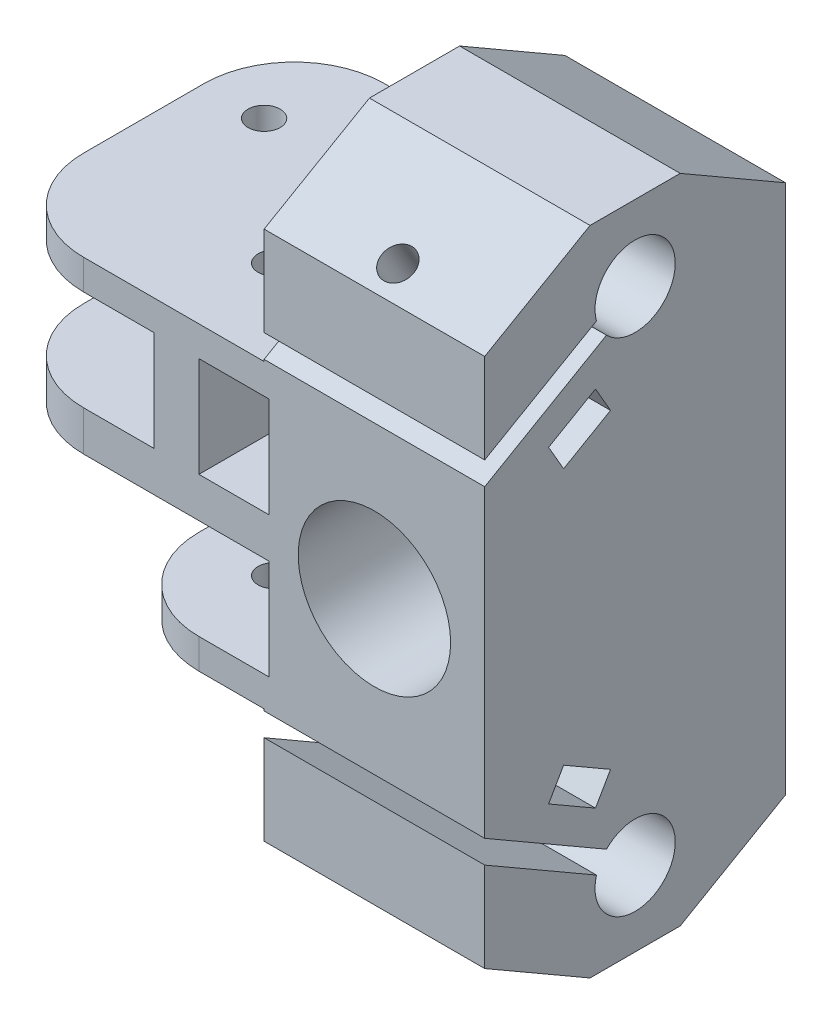
SolidWorks part; units mm, degrees
ref_plane "Plano frontal" through (0, 0, 0) normal (0, 0, 1) x (1, 0, 0)
ref_plane "Plano superior" through (0, 0, 0) normal (0, 1, 0) x (1, 0, 0)
ref_plane "Plano direito" through (0, 0, 0) normal (1, 0, 0) x (0, 0, -1)
sketch "Esboço2" plane through (0, 0, 0) normal (0, 0, 1) x (1, 0, 0)
  line L0 (-11, 15) -> (-11, 32.5)
  line L1 (-11, -32.5) -> (11, -32.5)
  line L2 (-11, -32.5) -> (-11, -15)
  line L3 (-11, 32.5) -> (11, 32.5)
  line L4 (11, -32.5) -> (11, 32.5)
  line L5 (-11, -32.5) -> (11, 32.5) construction
  line L6 (-11, 32.5) -> (11, -32.5) construction
  line L7 (-38, 15) -> (-11, 15)
  line L8 (-38, 15) -> (-38, 12)
  line L9 (-26.5, -15) -> (-11, -15)
  line L10 (0, 0) -> (-50.7474, 0) construction
  line L11 (-38, 15) -> (-11, -15) construction
  line L12 (-38, -15) -> (-11, 15) construction
  line L13 (-17.5, 2) -> (-10.5, 2)
  line L14 (-17.5, 2) -> (-17.5, 12)
  line L15 (-17.5, 12) -> (-10.5, 12)
  line L16 (-10.5, 2) -> (-10.5, 12)
  line L17 (-17.5, 2) -> (-10.5, 12) construction
  line L18 (-17.5, 12) -> (-10.5, 2) construction
  line L19 (-22, 12) -> (-38, 12)
  line L20 (-22, 12) -> (-22, 2)
  line L21 (-22, 2) -> (-38, 2)
  line L22 (-38, -2) -> (-26.5, -2)
  line L23 (-22, 12) -> (-38, 2) construction
  line L24 (-22, 2) -> (-38, 12) construction
  line L25 (-10.5, -2) -> (-26.5, -2)
  line L26 (-10.5, -2) -> (-10.5, -12)
  line L27 (-10.5, -12) -> (-26.5, -12)
  line L29 (-26.5, -12) -> (-26.5, -15)
  line L31 (-38, 2) -> (-38, -2)
  line L33 (-10.5, -2) -> (-26.5, -12) construction
  line L34 (-10.5, -12) -> (-26.5, -2) construction
  circle A0 centre (0, 0) radius 7.6
  point P7 (-24.5, 0)
  point P12 (-14, 7)
  point P18 (-30, 7)
  point P23 (-26.5, -15)
  point P26 (-18.5, -7)
  dimension "D1" = 15.2
  dimension "D2" = 65
  dimension "D3" = 22
  dimension "D4" = 30
  dimension "D5" = 27
  dimension "D6" = 3
  dimension "D7" = 7
  dimension "D9" = 16
  dimension "D10" = 0.5
  dimension "D11" = 10
  dimension "D12" = 3
extrude "Ressalto-extrusão1" add sketch "Esboço2" along normal blind 30
sketch "Esboço3" plane through (-11, 0, 0) normal (-1, 0, 0) x (0, 0, 1)
  line L0 (0, 0) -> (30, 0) construction
  line L1 (30, 15) -> (0, 15) construction
  line L2 (30, 26.4348) -> (19.4948, 32.5)
  line L3 (30, 32.5) -> (30, 15) construction
  line L4 (15, 32.5) -> (15, 15) construction
  line L5 (18.9522, 18.0994) -> (23.6287, 15.3994)
  line L6 (18.9522, 18.0994) -> (17.4522, 15.5013)
  line L7 (17.4522, 15.5013) -> (22.1287, 12.8013)
  line L8 (23.6287, 15.3994) -> (22.1287, 12.8013)
  line L9 (18.9522, 18.0994) -> (22.1287, 12.8013) construction
  line L10 (17.4522, 15.5013) -> (23.6287, 15.3994) construction
  line L12 (18.3535, 23.0639) -> (31.633, 15.3969) construction
  line L13 (17.8541, 22.1975) -> (31.133, 14.5309)
  line L14 (18.8541, 23.9295) -> (32.133, 16.2629)
  line L15 (15.5, 25.866) -> (32.133, 16.2629) construction
  line L16 (15, 25) -> (31.633, 15.3969) construction
  line L17 (14.5, 24.134) -> (31.133, 14.5309) construction
  line L18 (31.133, 14.5309) -> (32.133, 16.2629)
  line L19 (18.3535, -23.0639) -> (31.633, -15.3969) construction
  line L20 (17.4522, -15.5013) -> (23.6287, -15.3994) construction
  line L21 (18.9522, -18.0994) -> (22.1287, -12.8013) construction
  line L22 (31.133, -14.5309) -> (32.133, -16.2629)
  line L23 (18.8541, -23.9295) -> (32.133, -16.2629)
  line L24 (17.8541, -22.1975) -> (31.133, -14.5309)
  line L25 (23.6287, -15.3994) -> (22.1287, -12.8013)
  line L26 (17.4522, -15.5013) -> (22.1287, -12.8013)
  line L27 (18.9522, -18.0994) -> (17.4522, -15.5013)
  line L28 (18.9522, -18.0994) -> (23.6287, -15.3994)
  line L29 (30, 32.5) -> (0, 32.5) construction
  line L30 (30, 15) -> (0, 15) construction
  line L31 (0, 26.4348) -> (10.5052, 32.5)
  line L32 (0, 26.4348) -> (0, 32.5)
  line L33 (0, 32.5) -> (10.5052, 32.5)
  line L34 (30, 26.4348) -> (30, 32.5)
  line L35 (30, 32.5) -> (19.4948, 32.5)
  line L36 (30, -32.5) -> (19.4948, -32.5)
  line L37 (30, -26.4348) -> (30, -32.5)
  line L38 (0, -32.5) -> (10.5052, -32.5)
  line L39 (0, -26.4348) -> (0, -32.5)
  line L40 (0, -26.4348) -> (10.5052, -32.5)
  line L41 (30, -26.4348) -> (19.4948, -32.5)
  arc A0 (18.8541, 23.9295) -> (17.8541, 22.1975) centre (15, 25) ccw
  arc A1 (18.8541, -23.9295) -> (17.8541, -22.1975) centre (15, -25) cw
  point P11 (20.5404, 15.4504)
  point P33 (20.5404, -15.4504)
  point P37 (15, 32.5)
  dimension "D1" = 4
  dimension "D2" = 50
  dimension "D3" = 5.4
  dimension "D4" = 3
  dimension "D5" = 3
  dimension "D8" = 30
  dimension "D9" = 3
  dimension "D6" = 1
  dimension "D7" = 1
extrude "Corte-extrusão1" cut sketch "Esboço3" against normal through all
sketch "Esboço4" plane through (0, 15, 0) normal (0, 1, 0) x (1, 0, 0)
  line L1 (11, -15) -> (-38, -15) construction
  line L2 (11, -19.4948) -> (11, -10.5052) construction
  line L5 (-38, -30) -> (-38, 0) construction
  line L6 (-32, -9) -> (-32, -15) construction
  line L7 (-11, 0) -> (-38, 0) construction
  line L8 (-19, -21) -> (-19, -15) construction
  circle A0 centre (-32, -9) radius 1.6
  circle A1 centre (-32, -9) radius 5 construction
  circle A2 centre (-32, -9) radius 7 construction
  circle A3 centre (-19, -21) radius 1.6
  circle A4 centre (-19, -21) radius 5 construction
  point P16 (0, 0)
  dimension "D2" = 14
  dimension "D3" = 2
  dimension "D1" = 3.2
  dimension "D5" = 10
  dimension "D4" = 32
  dimension "D6" = 19
extrude "Corte-extrusão2" cut sketch "Esboço4" against normal through all both and the other way through all
fillet "Filete2" radius 9 6 edges at (-38, 13.5, 30) (-38, 0, 30) (-38, 0, 0) (-38, 13.5, 0) (-26.5, -13.5, 30) (-26.5, -13.5, 0)
sketch "Esboço7" plane through (0, 19.183, 11.0753) normal (0, 0.866, 0.5) x (1, 0, 0)
  line L0 (11, -7.3634) -> (-11, -7.3634) construction
  line L1 (11, -7.3634) -> (11, -12.7634) construction
  circle A0 centre (0, -10.0634) radius 1.6
  point P4 (0, -7.3634)
  point P7 (11, -10.0634)
  dimension "D1" = 3.2
extrude "Corte-extrusão3" cut sketch "Esboço7" against normal blind 10 and the other way through all
